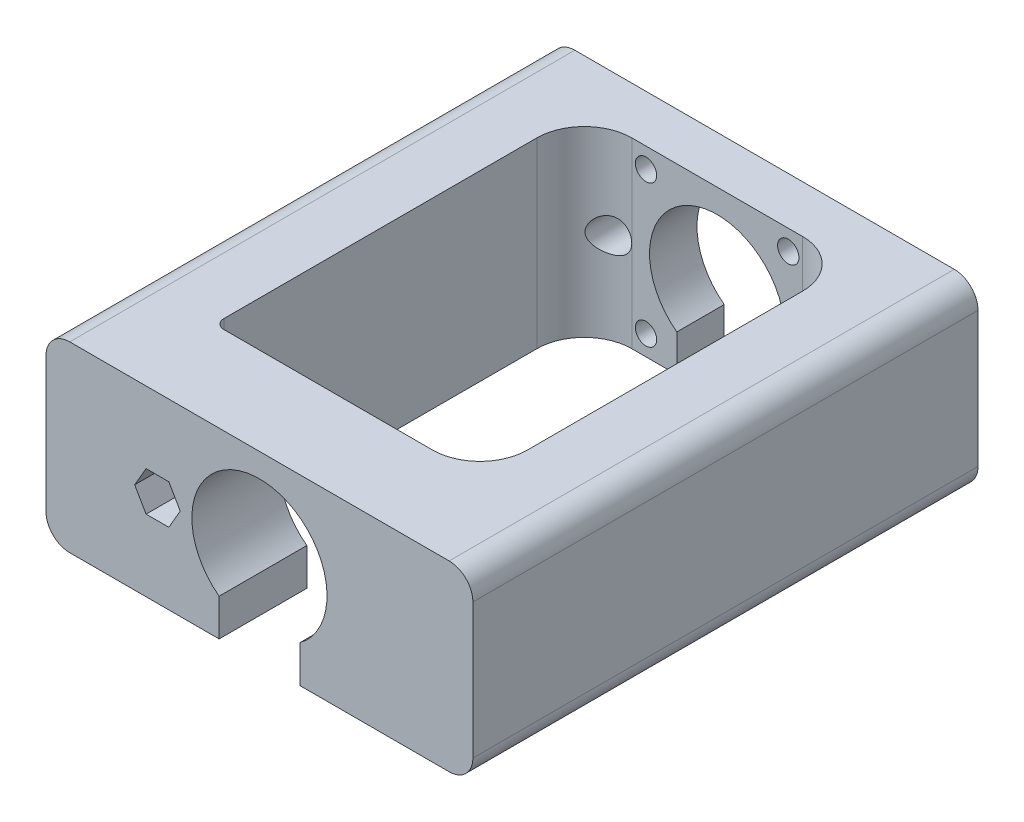
SolidWorks part; units mm, degrees
ref_plane "Front Plane" through (0, 0, 0) normal (0, 0, 1) x (1, 0, 0)
ref_plane "Top Plane" through (0, 0, 0) normal (0, 1, 0) x (1, 0, 0)
ref_plane "Right Plane" through (0, 0, 0) normal (1, 0, 0) x (0, 0, -1)
sketch "Sketch1" plane through (0, 0, 0) normal (0, 0, 1) x (1, 0, 0)
  line L0 (-15, 19.25) -> (-30, 19.25)
  line L2 (-45, 14.25) -> (-45, -14.25)
  line L4 (-15, 19.25) -> (15, 19.25)
  line L6 (15, -19.25) -> (8.5, -19.25)
  line L11 (-30, -19.25) -> (-15, -19.25)
  line L12 (-30, 19.25) -> (-40, 19.25)
  line L13 (-30, -19.25) -> (-40, -19.25)
  line L14 (-8.5, -19.25) -> (-15, -19.25)
  line L15 (0, 0) -> (0, 9.3162)
  line L16 (30, -19.25) -> (15, -19.25)
  line L17 (8.5, -16.75) -> (8.5, -11.4373)
  line L18 (-8.5, -16.75) -> (-8.5, -11.4373)
  line L19 (-8.5, -16.75) -> (-8.5, -19.25)
  line L20 (8.5, -16.75) -> (8.5, -19.25)
  line L21 (15, 19.25) -> (30, 19.25)
  line L22 (30, -19.25) -> (40, -19.25)
  line L23 (30, 19.25) -> (40, 19.25)
  line L24 (45, 14.25) -> (45, -14.25)
  arc A0 (8.5, -11.4373) -> (-8.5, -11.4373) centre (0, 0) ccw
  circle A1 centre (15, 15) radius 2.25
  circle A2 centre (-15, 15) radius 2.25
  circle A3 centre (-15, -15) radius 2.25
  circle A4 centre (15, -15) radius 2.25
  arc A19 (-40, -19.25) -> (-45, -14.25) centre (-40, -14.25) cw
  arc A20 (-40, 19.25) -> (-45, 14.25) centre (-40, 14.25) ccw
  arc A21 (40, 19.25) -> (45, 14.25) centre (40, 14.25) cw
  arc A22 (40, -19.25) -> (45, -14.25) centre (40, -14.25) ccw
  point P5 (19.25, 15)
  point P7 (-10.75, 15)
  point P13 (-10.75, -15)
  point P18 (-25.25, 0)
  point P19 (19.25, -15)
  point P20 (-15, 15)
  point P22 (15, 15)
  point P24 (15, -15)
  point P26 (-15, -15)
  point P38 (-39.75, 0)
  point P39 (-20.75, 0)
  point P51 (39.75, 0)
  dimension "D1" = 2
  dimension "D3" = 5
  dimension "D2" = 2
extrude "Boss-Extrude1" add sketch "Sketch1" along normal blind 10 contours A19 L11 L6 L4 A4 A3 A2 A1 A0 region at (0, 18.2711, 0)
sketch "Sketch2" plane through (0, 0, 10) normal (0, 0, 1) x (1, 0, 0)
  line L12 (-45, 14.25) -> (-45, -14.25)
  line L14 (-40, 19.25) -> (-28, 19.25)
  line L15 (-28, 0) -> (-28, 19.25)
  line L16 (-28, 0) -> (-28, -19.25)
  line L17 (-40, -19.25) -> (-28, -19.25)
  line L19 (40, -19.25) -> (28, -19.25)
  line L20 (28, 0) -> (28, -19.25)
  line L21 (28, 0) -> (28, 19.25)
  line L22 (40, 19.25) -> (28, 19.25)
  line L23 (45, 14.25) -> (45, -14.25)
  arc A0 (40, 19.25) -> (45, 14.25) centre (40, 14.25) cw
  arc A16 (-45, -14.25) -> (-40, -19.25) centre (-40, -14.25) ccw
  arc A17 (-40, 19.25) -> (-45, 14.25) centre (-40, 14.25) ccw
  arc A18 (45, -14.25) -> (40, -19.25) centre (40, -14.25) cw
extrude "Boss-Extrude3" add sketch "Sketch2" along normal blind 78 separate body
sketch "Sketch4" plane through (0, 0, 88) normal (0, 0, 1) x (1, 0, 0)
  line L5 (-28, -19.25) -> (-28, 19.25)
  line L7 (-45, 14.25) -> (-45, -14.25)
  line L11 (-45, 14.25) -> (-45, -14.25)
  line L21 (-40, 19.25) -> (40, 19.25)
  line L22 (-40, -19.25) -> (-8.5, -19.25)
  line L23 (-40, -19.25) -> (-28, -19.25)
  line L25 (-28, 19.25) -> (-40, 19.25)
  line L27 (-8.5, -11.4373) -> (-8.5, -19.25) construction
  line L28 (8.5, -19.25) -> (8.5, -11.4373) construction
  line L29 (40, 19.25) -> (28, 19.25)
  line L30 (28, 19.25) -> (28, -19.25)
  line L31 (28, -19.25) -> (40, -19.25)
  line L32 (45, -14.25) -> (45, 14.25)
  line L36 (45, -14.25) -> (45, 14.25)
  line L37 (-8.5, -11.4373) -> (-8.5, -19.25)
  line L38 (8.5, -19.25) -> (8.5, -11.4373)
  line L39 (8.5, -19.25) -> (40, -19.25)
  circle A1 centre (-21.5, 0) radius 3.5
  arc A2 (-45, -14.25) -> (-40, -19.25) centre (-40, -14.25) ccw
  arc A3 (-40, 19.25) -> (-45, 14.25) centre (-40, 14.25) ccw
  arc A4 (-45, -14.25) -> (-40, -19.25) centre (-40, -14.25) ccw
  arc A5 (-40, 19.25) -> (-45, 14.25) centre (-40, 14.25) ccw
  arc A11 (8.5, -11.4373) -> (-8.5, -11.4373) centre (0, 0) ccw construction
  arc A12 (45, 14.25) -> (40, 19.25) centre (40, 14.25) ccw
  arc A13 (40, -19.25) -> (45, -14.25) centre (40, -14.25) ccw
  arc A14 (45, 14.25) -> (40, 19.25) centre (40, 14.25) ccw
  arc A15 (40, -19.25) -> (45, -14.25) centre (40, -14.25) ccw
  arc A17 (8.5, -11.4373) -> (-8.5, -11.4373) centre (0, 0) ccw
  dimension "D3" = 0
  dimension "D1" = 0
extrude "Boss-Extrude4" add sketch "Sketch4" along normal blind 10
sketch "Sketch6" plane through (0, 0, 98) normal (0, 0, 1) x (1, 0, 0)
  line L6 (-40, -19.25) -> (-8.5, -19.25)
  line L8 (-40, -19.25) -> (-8.5, -19.25)
  line L9 (45, -14.25) -> (45, 14.25)
  line L10 (-45, 14.25) -> (-45, -14.25)
  line L11 (45, -14.25) -> (45, 14.25)
  line L16 (-45, 14.25) -> (-45, -14.25)
  line L21 (-16.7, 0) -> (-19.1, 4.1569)
  line L22 (-19.1, 4.1569) -> (-23.9, 4.1569)
  line L23 (-23.9, 4.1569) -> (-26.3, 0)
  line L24 (40, 19.25) -> (-40, 19.25)
  line L25 (40, 19.25) -> (-40, 19.25)
  line L26 (-26.3, 0) -> (-23.9, -4.1569)
  line L27 (-23.9, -4.1569) -> (-19.1, -4.1569)
  line L28 (-19.1, -4.1569) -> (-16.7, 0)
  line L30 (8.5, -11.4373) -> (8.5, -19.25)
  line L31 (8.5, -11.4373) -> (8.5, -19.25)
  line L32 (8.5, -19.25) -> (40, -19.25)
  line L33 (8.5, -19.25) -> (40, -19.25)
  line L34 (-8.5, -19.25) -> (-8.5, -11.4373)
  line L35 (-8.5, -19.25) -> (-8.5, -11.4373)
  circle A0 centre (-21.5, 0) radius 4.8 construction
  arc A5 (40, -19.25) -> (45, -14.25) centre (40, -14.25) ccw
  arc A6 (40, -19.25) -> (45, -14.25) centre (40, -14.25) ccw
  arc A9 (45, 14.25) -> (40, 19.25) centre (40, 14.25) ccw
  arc A10 (-40, 19.25) -> (-45, 14.25) centre (-40, 14.25) ccw
  arc A11 (-45, -14.25) -> (-40, -19.25) centre (-40, -14.25) ccw
  arc A16 (-40, 19.25) -> (-45, 14.25) centre (-40, 14.25) ccw
  arc A17 (-45, -14.25) -> (-40, -19.25) centre (-40, -14.25) ccw
  arc A18 (45, 14.25) -> (40, 19.25) centre (40, 14.25) ccw
  arc A20 (8.5, -11.4373) -> (-8.5, -11.4373) centre (0, 0) ccw
  arc A21 (8.5, -11.4373) -> (-8.5, -11.4373) centre (0, 0) ccw
  dimension "D1" = 0
extrude "Boss-Extrude5" add sketch "Sketch6" along normal blind 8.5
sketch "Sketch5" plane through (0, 0, 98) normal (0, 0, 1) x (1, 0, 0)
  circle A0 centre (-21.5, 0) radius 3.5
extrude "Cut-Extrude1" cut sketch "Sketch5" against normal through all
combine bodies "Combine1" operation type add bodies to combine 110 111 113
fillet "Fillet2" radius 2 1 edges at (-28, 0, 88)
fillet "Fillet3" radius 10 3 edges at (-28, 0, 10) (28, 0, 88) (28, 0, 10)
